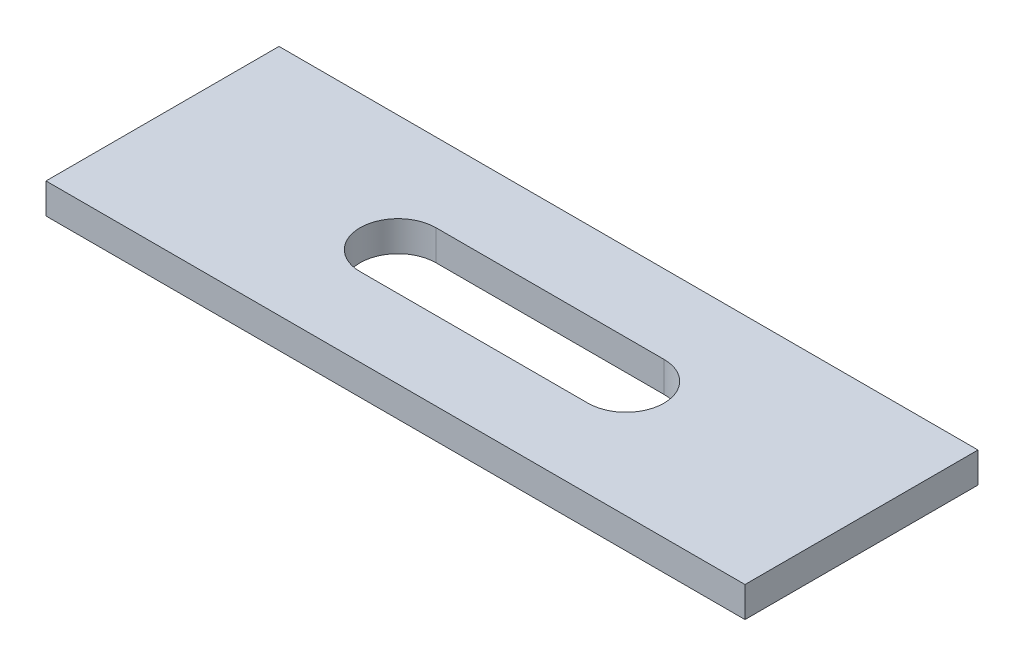
SolidWorks part; units mm, degrees
material "Pine"
ref_plane "Front Plane" through (0, 0, 0) normal (0, 0, 1) x (1, 0, 0)
ref_plane "Top Plane" through (0, 0, 0) normal (0, 1, 0) x (1, 0, 0)
ref_plane "Right Plane" through (0, 0, 0) normal (1, 0, 0) x (0, 0, -1)
sketch "Sketch2" plane through (0, 0, 0) normal (0, 1, 0) x (1, 0, 0)
  line L4 (93, 46) -> (183, 46) construction
  line L5 (0, 0) -> (276, 0)
  line L6 (0, 0) -> (0, 92)
  line L7 (0, 92) -> (276, 92)
  line L8 (276, 0) -> (276, 92)
  line L9 (93, 61) -> (183, 61)
  line L10 (93, 31) -> (183, 31)
  arc A0 (93, 61) -> (93, 31) centre (93, 46) ccw
  arc A1 (183, 31) -> (183, 61) centre (183, 46) ccw
  point P7 (138, 46)
  dimension "D3" = 46
  dimension "D5" = 15
  dimension "D1" = 92
  dimension "D2" = 276
  dimension "D4" = 93
  dimension "D6" = 90
extrude "Boss-Extrude1" add sketch "Sketch2" along normal blind 12 contours L7 L8 L5 L6
extrude "Cut-Extrude1" cut sketch "Sketch2<3>" along normal up to surface (12 mm away) contours A0 L10 A1 L9 up to face at (138, 12, -46)
sketch "Sketch2<3>" plane through (0, 0, 0) normal (0, 1, 0) x (1, 0, 0) same geometry as "Sketch2"
